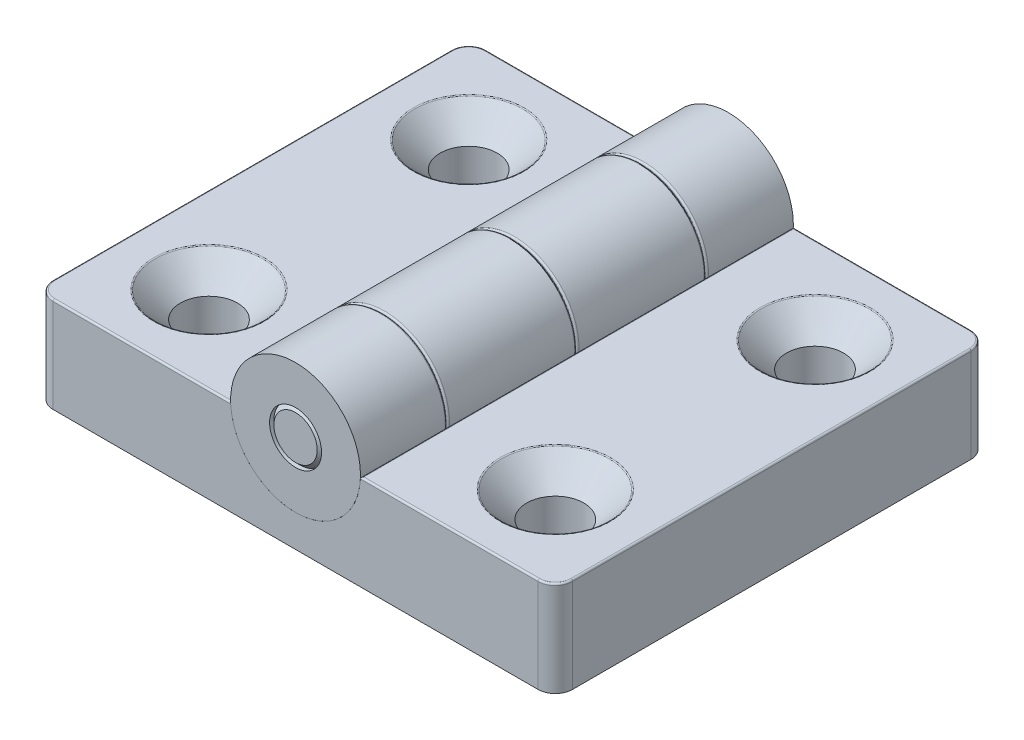
SolidWorks part; units mm, degrees
ref_plane "前视基准面" through (0, 0, 0) normal (0, 0, 1) x (1, 0, 0)
ref_plane "上视基准面" through (0, 0, 0) normal (0, 1, 0) x (1, 0, 0)
ref_plane "右视基准面" through (0, 0, 0) normal (1, 0, 0) x (0, 0, -1)
sketch "草图1" plane through (0, 0, 0) normal (0, 0, 1) x (1, 0, 0)
  circle A0 centre (0, 0) radius 7.5
  circle A1 centre (0, 0) radius 3
  dimension "D1" = 15
  dimension "D2" = 6
extrude "凸台-拉伸1" add sketch "草图1" along normal mid plane 50
sketch "草图2" plane through (0, 0, 0) normal (0, 0, 1) x (1, 0, 0)
  circle A0 centre (0, 0) radius 3
  dimension "D1" = 6
extrude "凸台-拉伸2" add sketch "草图2" along normal mid plane 50 separate body
chamfer "倒角1" distance 0.5 angle 45 1 edges at (3, 0, 25)
sketch "草图3" plane through (0, 0, 0) normal (0, 1, 0) x (1, 0, 0)
  line L0 (0, 0) -> (14.2235, 0) construction
  line L1 (7.5, 15) -> (5.5, 15)
  line L2 (7.5, 15) -> (7.5, 14.9)
  line L3 (7.5, 14.9) -> (5.5, 14.9)
  line L4 (5.5, 15) -> (5.5, 14.9)
  line L5 (7.5, 25) -> (-7.5, 25) construction
  line L6 (-7.5, -25) -> (7.5, -25) construction
  line L7 (7.5, -25) -> (7.5, 25) construction
  line L9 (7.5, 0.05) -> (5.5, 0.05)
  line L10 (7.5, 0.05) -> (7.5, -0.05)
  line L11 (7.5, -0.05) -> (5.5, -0.05)
  line L12 (5.5, 0.05) -> (5.5, -0.05)
  line L13 (7.5, -14.9) -> (4.8947, -14.9)
  line L14 (7.5, -14.9) -> (7.5, -15)
  line L15 (7.5, -15) -> (4.8947, -15)
  line L16 (4.8947, -14.9) -> (4.8947, -15)
  point P4 (7.5, 0)
  dimension "D1" = 10
  dimension "D2" = 0.1
  dimension "D3" = 10
  dimension "D4" = 2
revolve "切除-旋转1" cut sketch "草图3" angle 360 about axis through (0, 0, 25) along (0, 0, -1)
fillet "圆角1" radius 0.2 6 edges at (7.5, 0, 15) (7.5, 0, 14.9) (7.5, 0, 0.05) (7.5, 0, -0.05) (7.5, 0, -14.9) (7.5, 0, -15)
sketch "草图4" plane through (0, 0, 0) normal (0, 1, 0) x (1, 0, 0)
  line L0 (-7.5, -25) -> (7.5, -25) construction
  line L1 (-19.5, 25) -> (19.5, 25)
  line L2 (-19.5, 25) -> (-19.5, -25)
  line L3 (-19.5, -25) -> (19.5, -25)
  line L4 (19.5, 25) -> (19.5, -25)
  line L5 (7.5, 25) -> (-7.5, 25) construction
  point P4 (0, -25)
  dimension "D1" = 39
sketch "草图5" plane through (0, 0, -25) normal (0, 0, -1) x (-1, 0, 0)
  line L0 (7.4973, -0.2) -> (30, -0.2)
  line L3 (-30, -0.2) -> (-7.4973, -0.2)
  line L4 (-30, -0.2) -> (-30, -11.2)
  line L5 (-30, -11.2) -> (30, -11.2)
  line L6 (30, -0.2) -> (30, -11.2)
  circle A0 centre (0, 0) radius 7.5 construction
  arc A1 (-7.4973, -0.2) -> (7.4973, -0.2) centre (0, 0) ccw
  dimension "D2" = 0.2
  dimension "D4" = 30
  dimension "D1" = 11
  dimension "D3" = 60
extrude "凸台-拉伸6" add sketch "草图5" against normal up to surface (50 mm away) separate body up to face at (7.5, 0, 25)
hole_wizard "M6 平头机械螺钉的锥形沉头孔1" positions "草图7" profile "草图6" countersink size "M6" standard "Ansi Metric" end condition through all
sketch "草图7" plane through (0, -0.2, 0) normal (0, 1, 0) x (-1, 0, 0)
  line L0 (0, 0) -> (0, 18.3669) construction
  line L2 (0, 0) -> (27.3768, 0) construction
  point P1 (20, -15)
  point P3 (-20, -15)
  point P5 (20, 15)
  point P7 (-20, 15)
  dimension "D1" = 40
  dimension "D2" = 30
sketch "草图6" plane through (-20, -0.2, -15) normal (1, 0, 0) x (0, 0, 1)
  line L0 (0, 0) -> (0, 11)
  line L1 (0, 11) -> (3.3, 11)
  line L2 (3.3, 11) -> (3.3, 3)
  line L3 (3.3, 3) -> (6.3, 0)
  line L5 (6.3, 0) -> (0, 0)
  line L6 (-3.3, 3) -> (-6.3, 0) construction
  line L11 (0, -6.35) -> (0, 107.95) construction
  dimension "通孔孔直径" = 6.6
  dimension "通孔孔深度" = 11
  dimension "近端锥形沉头孔直径" = 12.6
  dimension "近端锥形沉头孔角度" = 90
fillet "圆角2" radius 0.2 12 edges at (18.7487, -0.2, -25) (30, -0.2, 0) (18.7487, -0.2, 25) (7.4973, -0.2, 0) (20, -0.2, 21.3) (20, -0.2, -8.7) (-18.7487, -0.2, -25) (-7.4973, -0.2, 0) (-18.7487, -0.2, 25) (-30, -0.2, 0) (-20, -0.2, 21.3) (-20, -0.2, -8.7)
fillet "圆角3" radius 2 8 edges at (-29.9414, -0.2586, -24.9414) (29.9414, -0.2586, -24.9414) (29.9414, -0.2586, 24.9414) (-29.9414, -0.2586, 24.9414) (-30, -5.8, 25) (30, -5.8, 25) (30, -5.8, -25) (-30, -5.8, -25)
chamfer "倒角2" distance 0.5 angle 45 1 edges at (3, 0, -25)
